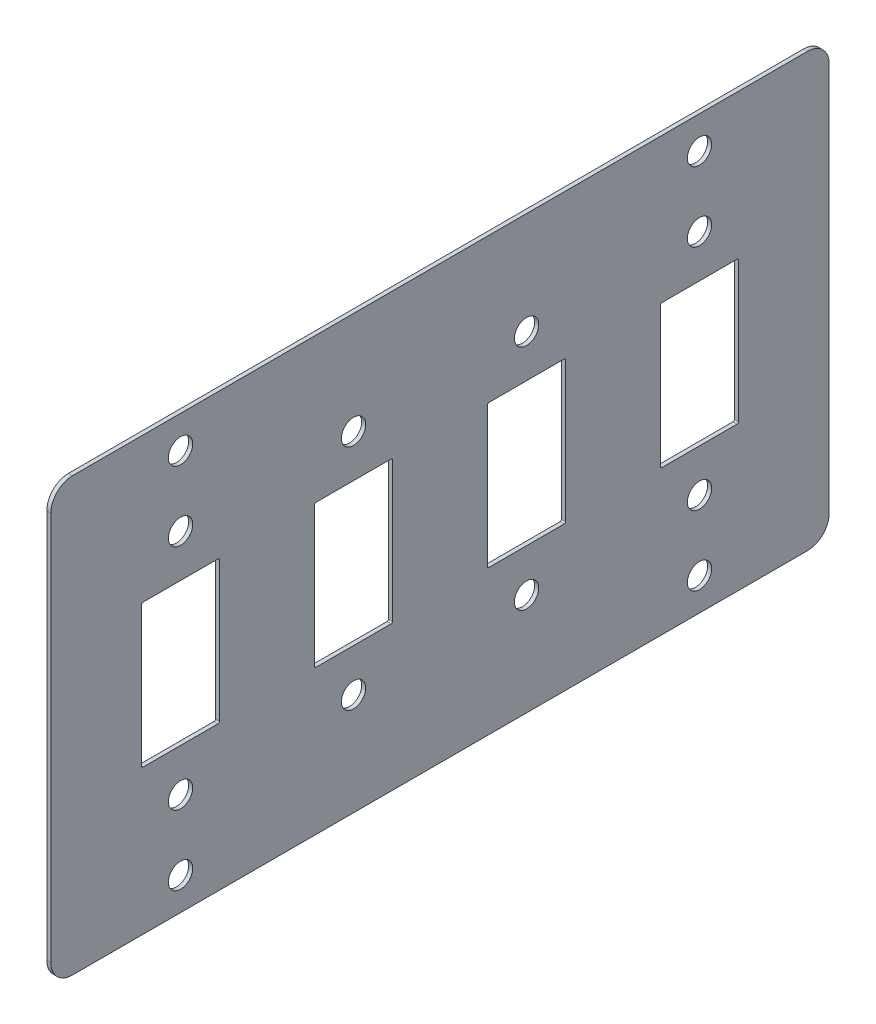
SolidWorks part; units mm, degrees
material "SH,Plain Carbon"
ref_plane "Front" through (0, 0, 0) normal (0, 0, 1) x (1, 0, 0)
ref_plane "Top" through (0, 0, 0) normal (0, 1, 0) x (1, 0, 0)
ref_plane "Right" through (0, 0, 0) normal (1, 0, 0) x (0, 0, -1)
sketch "Sketch1" plane through (0, 0, 0) normal (1, 0, 0) x (0, 0, -1)
  line L1 (114.3, -63.5) -> (-114.3, -63.5)
  line L2 (114.3, -63.5) -> (114.3, 63.5)
  line L3 (114.3, 63.5) -> (-114.3, 63.5)
  line L4 (-114.3, -63.5) -> (-114.3, 63.5)
  line L5 (114.3, -63.5) -> (-114.3, 63.5) construction
  line L6 (114.3, 63.5) -> (-114.3, -63.5) construction
  point P0 (0, 0)
  dimension "D1" = 228.6
  dimension "D2" = 127
base flange "Base-Flange1" sketch "Sketch1" thickness 1.1938 reverse thickness direction no parameters "D1"=1.4986
sketch "Sketch6" plane through (0, 0, 0) normal (1, 0, 0) x (0, 0, -1)
  line L0 (-114.3, 63.5) -> (-114.3, -63.5) construction
  line L1 (-87.6459, -20.9709) -> (-64.7541, -20.9709)
  line L2 (-87.6459, -20.9709) -> (-87.6459, 20.9709)
  line L3 (-87.6459, 20.9709) -> (-64.7541, 20.9709)
  line L4 (-64.7541, -20.9709) -> (-64.7541, 20.9709)
  line L5 (-87.6459, -20.9709) -> (-64.7541, 20.9709) construction
  line L6 (-87.6459, 20.9709) -> (-64.7541, -20.9709) construction
  line L7 (-76.2, 0) -> (-141.2374, 0) construction
  circle A0 centre (-76.2, 33.5026) radius 3.5719
  circle A1 centre (-76.2, -33.5026) radius 3.5719
  point P0 (-76.2, 0)
  dimension "D4" = 7.1437
  dimension "D1" = 22.8917
  dimension "D2" = 41.9417
  dimension "D3" = 38.1
  dimension "D5" = 67.0052
extrude "Cut-Extrude1" cut sketch "Sketch6" against normal up to next normal cut yes
pattern_linear "LPattern1" count 4 spacing 50.8 along (0, 0, -1) of "Cut-Extrude1"
sketch "Sketch7" plane through (0, 0, 0) normal (1, 0, 0) x (0, 0, -1)
  line L0 (-114.3, 63.5) -> (-114.3, -63.5) construction
  circle A0 centre (-76.2, 53.975) radius 3.5719
  dimension "D3" = 7.1437
  dimension "D1" = 38.1
  dimension "D2" = 53.975
extrude "Cut-Extrude2" cut sketch "Sketch7" against normal up to next normal cut yes
mirror "Mirror1" about plane through (0, 0, 0) normal (0, 0, 1) of "Cut-Extrude2"
mirror "Mirror2" about plane through (0, 0, 0) normal (0, 1, 0) of "Mirror1", "Cut-Extrude2"
fillet "Fillet1" radius 6.35 4 edges at (-0.5969, -63.5, 114.3) (-0.5969, -63.5, -114.3) (-0.5969, 63.5, 114.3) (-0.5969, 63.5, -114.3)
fillet "Fillet2" radius 0.3969 16 edges at (-0.5969, -20.9709, -87.6459) (-0.5969, -20.9709, -64.7541) (-0.5969, 20.9709, -64.7541) (-0.5969, 20.9709, -87.6459) (-0.5969, -20.9709, -36.8459) (-0.5969, -20.9709, -13.9541) (-0.5969, 20.9709, -13.9541) (-0.5969, 20.9709, -36.8459) (-0.5969, 20.9709, 87.6459) (-0.5969, 20.9709, 64.7541) (-0.5969, -20.9709, 64.7541) (-0.5969, -20.9709, 36.8459) (-0.5969, 20.9709, 36.8459) (-0.5969, 20.9709, 13.9541) (-0.5969, -20.9709, 13.9541) (-0.5969, -20.9709, 87.6459)
other "LaserCutPropertyMigration-DeleteAfterThisAppears1"
sketch "Bend-Lines1" [suppressed] plane through (0, 0, 0) normal (0, 1, 0) x (1, 0, 0)
sketch "Bounding-Box1" [suppressed] plane through (0, 0, 0) normal (0, 1, 0) x (1, 0, 0)
sheet metal parameters "Sheet-Metal28" thickness 1.1938 parameters "D1"=1.4986
flat pattern "Flat-Pattern28" [suppressed]
sketch "Bend-Lines2" plane through (0, 0, 0) normal (0, 1, 0) x (1, 0, 0)
sketch3d "Bounding-Box2" [suppressed]
  line L0 (171.45, -63.5, 0) -> (-171.45, -63.5, 0) construction
  line L1 (171.45, 63.5, 0) -> (-171.45, 63.5, 0) construction
  line L2 (171.45, -63.5, 0) -> (171.45, 63.5, 0) construction
  line L3 (-171.45, -63.5, 0) -> (-171.45, 63.5, 0) construction
sheet metal parameters "Sheet-Metal29" thickness 1.1938 parameters "D1"=1.4986
flat pattern "Flat-Pattern28"
sketch "Bend-Lines2" plane through (0, 0, 0) normal (0, 1, 0) x (1, 0, 0)
sketch3d "Bounding-Box2" [suppressed]
  line L0 (-171.45, -63.5, 0) -> (171.45, -63.5, 0) construction
  line L1 (-171.45, 63.5, 0) -> (171.45, 63.5, 0) construction
  line L2 (-171.45, -63.5, 0) -> (-171.45, 63.5, 0) construction
  line L3 (171.45, -63.5, 0) -> (171.45, 63.5, 0) construction
sheet metal parameters "Sheet-Metal30" thickness 1.1938 parameters "D1"=1.4986
flat pattern "Flat-Pattern28"
sketch "Bend-Lines2" plane through (0, 0, 0) normal (0, 1, 0) x (1, 0, 0)
sketch3d "Bounding-Box2" [suppressed]
  line L0 (-95.25, -63.5, 0) -> (95.25, -63.5, 0) construction
  line L1 (-95.25, 63.5, 0) -> (95.25, 63.5, 0) construction
  line L2 (-95.25, -63.5, 0) -> (-95.25, 63.5, 0) construction
  line L3 (95.25, -63.5, 0) -> (95.25, 63.5, 0) construction
sheet metal parameters "Sheet-Metal31" thickness 1.1938 parameters "D1"=1.4986
flat pattern "Flat-Pattern28"
sketch "Bend-Lines2" plane through (0, 0, 0) normal (0, 1, 0) x (1, 0, 0)
sketch3d "Bounding-Box2" [suppressed]
  line L0 (-171.45, -63.5, 0) -> (171.45, -63.5, 0) construction
  line L1 (-171.45, 63.5, 0) -> (171.45, 63.5, 0) construction
  line L2 (-171.45, -63.5, 0) -> (-171.45, 63.5, 0) construction
  line L3 (171.45, -63.5, 0) -> (171.45, 63.5, 0) construction
sheet metal parameters "Sheet-Metal32" thickness 1.1938 parameters "D1"=1.4986
flat pattern "Flat-Pattern28"
sketch "Bend-Lines2" plane through (0, 0, 0) normal (0, 1, 0) x (1, 0, 0)
sketch3d "Bounding-Box2" [suppressed]
  line L0 (-171.45, -63.5, 0) -> (171.45, -63.5, 0) construction
  line L1 (-171.45, 63.5, 0) -> (171.45, 63.5, 0) construction
  line L2 (-171.45, -63.5, 0) -> (-171.45, 63.5, 0) construction
  line L3 (171.45, -63.5, 0) -> (171.45, 63.5, 0) construction
sheet metal parameters "Sheet-Metal33" thickness 1.1938 parameters "D1"=1.4986
flat pattern "Flat-Pattern28"
sketch "Bend-Lines2" plane through (0, 0, 0) normal (0, 1, 0) x (1, 0, 0)
sketch3d "Bounding-Box2" [suppressed]
  line L0 (-114.3, 63.5, 0) -> (114.3, 63.5, 0) construction
  line L1 (-114.3, -63.5, 0) -> (114.3, -63.5, 0) construction
  line L2 (-114.3, 63.5, 0) -> (-114.3, -63.5, 0) construction
  line L3 (114.3, 63.5, 0) -> (114.3, -63.5, 0) construction
equation "\"Total Cutting Length\"= \"Cutting Length-Outer\" + \"Cutting Length-Inner\""
equation "\"Amount in ft^2\"= \"Bounding Box Area-Blank\" / 144"
